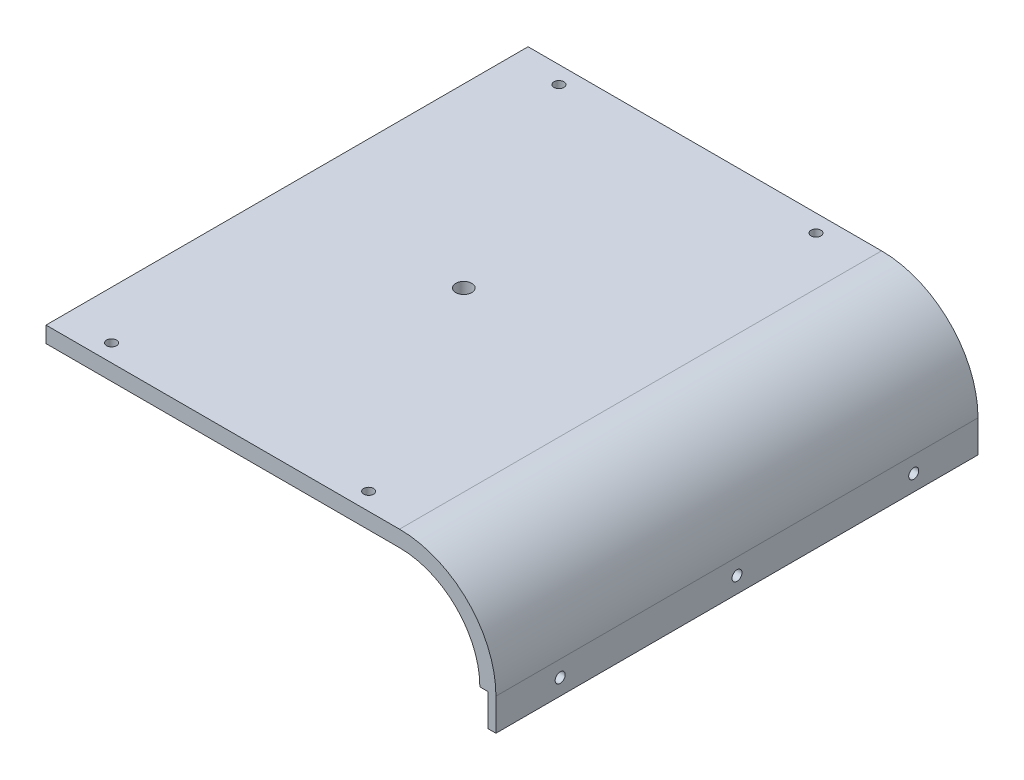
SolidWorks part; units mm, degrees
material "6061-T6 Aluminum"
ref_plane "Front Plane" through (0, 0, 0) normal (0, 0, 1) x (1, 0, 0)
ref_plane "Top Plane" through (0, 0, 0) normal (0, 1, 0) x (1, 0, 0)
ref_plane "Right Plane" through (0, 0, 0) normal (1, 0, 0) x (0, 0, -1)
sketch "Sketch1" plane through (0, 0, 0) normal (0, 0, 1) x (1, 0, 0)
  line L0 (-139.7, 0) -> (139.7, 0)
  line L1 (139.7, 0) -> (139.7, -152.4) construction
  line L2 (139.7, -76.2) -> (215.9, -76.2) construction
  line L3 (-139.7, -12.7) -> (139.7, -12.7)
  line L4 (-139.7, 0) -> (-139.7, -12.7)
  line L5 (215.9, -76.2) -> (203.2, -76.2)
  circle A0 centre (139.7, -76.2) radius 76.2 construction
  arc A1 (139.7, 0) -> (215.9, -76.2) centre (139.7, -76.2) cw
  arc A2 (139.7, -12.7) -> (203.2, -76.2) centre (139.7, -76.2) cw
  point P4 (0, 0)
  dimension "D1" = 152.4
  dimension "D2" = 355.6
  dimension "D3" = 12.7
extrude "Boss-Extrude1" add sketch "Sketch1" along normal blind 190.5 and the other way blind 190.5
sketch "Sketch2" plane through (0, -76.2, 0) normal (0, -1, 0) x (1, 0, 0)
  line L0 (203.2, 190.5) -> (215.9, 190.5) construction
  line L1 (209.55, 190.5) -> (215.9, 190.5)
  line L2 (209.55, 190.5) -> (209.55, -190.5)
  line L3 (209.55, -190.5) -> (215.9, -190.5)
  line L4 (215.9, 190.5) -> (215.9, -190.5)
extrude "Boss-Extrude2" add sketch "Sketch2" along normal blind 25.4
sketch "Sketch3" plane through (215.9, 0, 0) normal (1, 0, 0) x (0, 0, -1)
  line L0 (-190.5, -88.9) -> (190.5, -88.9) construction
  line L1 (-190.5, -101.6) -> (-190.5, -76.2) construction
  line L2 (190.5, -101.6) -> (190.5, -76.2) construction
  line L3 (0, -76.2) -> (0, -101.6) construction
  line L4 (190.5, -76.2) -> (-190.5, -76.2) construction
  line L5 (190.5, -101.6) -> (-190.5, -101.6) construction
  line L6 (139.7, -76.2) -> (139.7, -101.6) construction
  line L7 (-139.7, -76.2) -> (-139.7, -101.6) construction
  circle A0 centre (-139.7, -88.9) radius 3.9687
  circle A1 centre (0, -88.9) radius 3.9687
  circle A2 centre (139.7, -88.9) radius 3.9687
  dimension "D3" = 7.9375
  dimension "D1" = 139.7
  dimension "D2" = 139.7
extrude "Cut-Extrude1" cut sketch "Sketch3" against normal blind 25.4
sketch "Sketch4" plane through (0, 0, 0) normal (0, 1, 0) x (1, 0, 0)
  circle A0 centre (0, 0) radius 6.35
  dimension "D1" = 12.7
extrude "Cut-Extrude2" cut sketch "Sketch4" against normal blind 17.78
sketch "Sketch7" plane through (0, 0, 0) normal (0, 1, 0) x (1, 0, 0)
  line L0 (139.7, 0) -> (101.6, 0) construction
  line L1 (101.6, 0) -> (0, 0) construction
  line L2 (0, 0) -> (-101.6, 0) construction
  line L3 (-101.6, 0) -> (-139.7, 0) construction
  line L4 (-101.6, -176.784) -> (-101.6, 176.784) construction
  line L5 (0, -176.784) -> (0, 176.784) construction
  line L6 (101.6, -176.784) -> (101.6, 176.784) construction
  line L7 (139.7, 190.5) -> (139.7, -190.5) construction
  line L8 (-139.7, 190.5) -> (-139.7, -190.5) construction
  line L9 (139.7, 190.5) -> (-139.7, 190.5) construction
  circle A0 centre (101.6, 176.784) radius 3.937
  circle A1 centre (-101.6, 176.784) radius 3.937
  circle A2 centre (101.6, -176.784) radius 3.937
  circle A3 centre (-101.6, -176.784) radius 3.937
  point P7 (-101.6, 0)
  point P10 (0, 0)
  point P13 (101.6, 0)
  point P18 (0, 0)
  point P19 (139.7, 0)
  point P23 (0, 0)
  point P24 (-139.7, 0)
  dimension "D2" = 7.874
  dimension "D3" = 13.716
  dimension "D1" = 203.2
extrude "Cut-Extrude3" cut sketch "Sketch7" against normal through all
